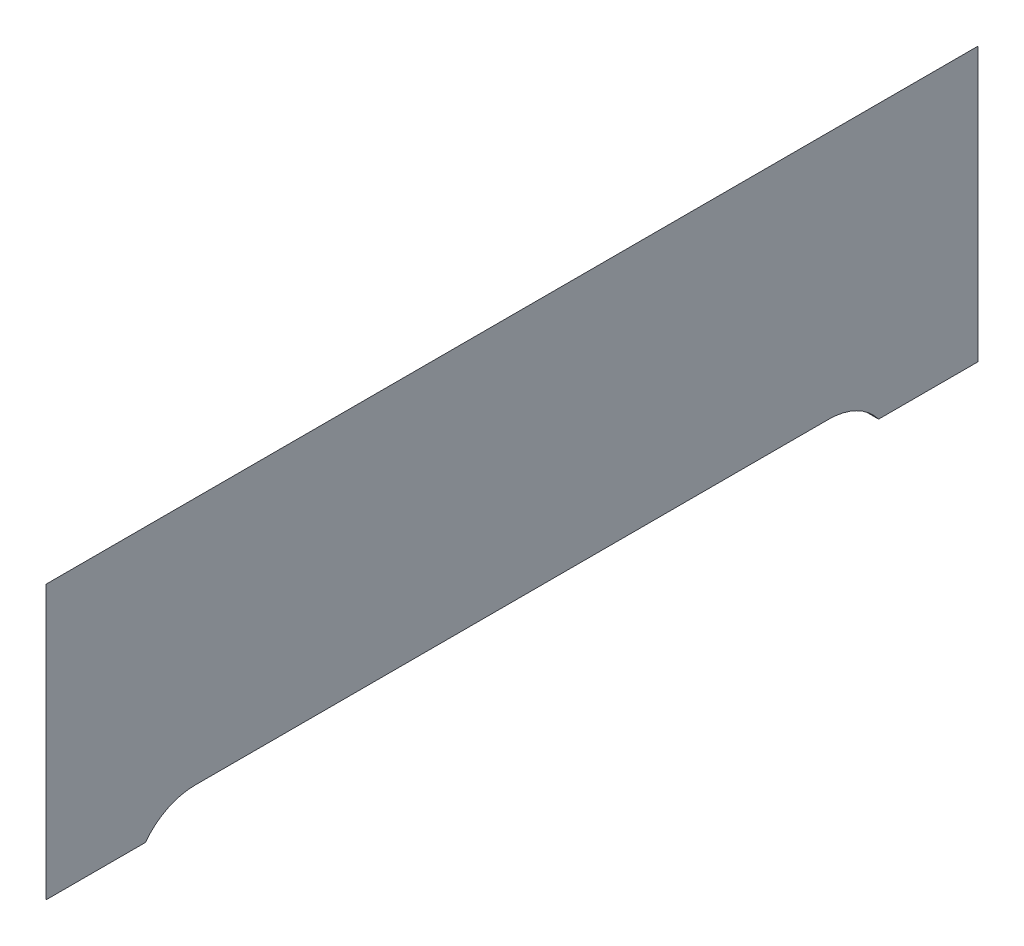
SolidWorks part; units mm, degrees
material "Teak"
ref_plane "Front Plane" through (0, 0, 0) normal (0, 0, 1) x (1, 0, 0)
ref_plane "Top Plane" through (0, 0, 0) normal (0, 1, 0) x (1, 0, 0)
ref_plane "Right Plane" through (0, 0, 0) normal (1, 0, 0) x (0, 0, -1)
sketch "Sketch1" plane through (0, 0, 0) normal (1, 0, 0) x (0, 0, -1)
  line L0 (0, 0) -> (0, -10)
  line L1 (60, 0) -> (315, 0)
  line L2 (0, 0) -> (0, 100)
  line L3 (0, 100) -> (375, 100)
  line L4 (375, 0) -> (375, 100)
  line L5 (0, -10) -> (40, -10)
  line L6 (375, 0) -> (375, -10)
  line L7 (375, -10) -> (335, -10)
  arc A0 (40, -10) -> (60, 0) centre (60, -25) cw
  arc A1 (335, -10) -> (315, 0) centre (315, -25) ccw
  dimension "D5" = 25
  dimension "D7" = 25
  dimension "D1" = 375
  dimension "D2" = 100
  dimension "D3" = 10
  dimension "D4" = 40
  dimension "D6" = 10
  dimension "D8" = 10
  dimension "D9" = 40
  dimension "D10" = 10
extrude "Boss-Extrude1" add sketch "Sketch1" along normal blind 12
chamfer "Chamfer1" distance 12 angle 45 3 edges at (0, 45, -375) (0, 45, 0) (0, 100, -187.5)
